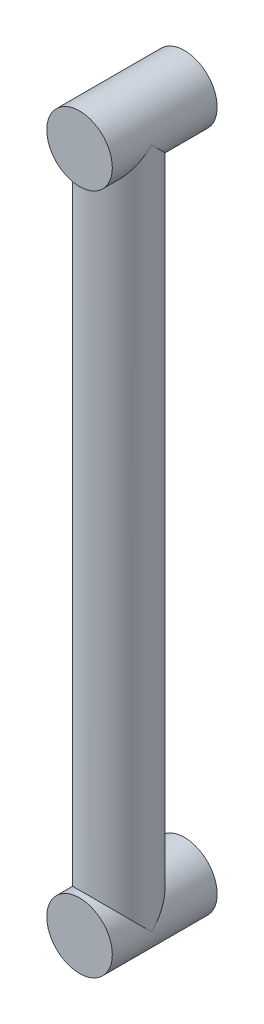
SolidWorks part; units mm, degrees
ref_plane "前视基准面" through (0, 0, 0) normal (0, 0, 1) x (1, 0, 0)
ref_plane "上视基准面" through (0, 0, 0) normal (0, 1, 0) x (1, 0, 0)
ref_plane "右视基准面" through (0, 0, 0) normal (1, 0, 0) x (0, 0, -1)
sketch "草图1" plane through (0, 0, 0) normal (0, 0, 1) x (1, 0, 0)
  circle A0 centre (0, 0) radius 250
extrude "凸台-拉伸1" add sketch "草图1" along normal blind 800
sketch "草图2" plane through (0, 0, 0) normal (0, 1, 0) x (1, 0, 0)
  circle A0 centre (0, -500) radius 250
  dimension "D1" = 500
extrude "凸台-拉伸2" add sketch "草图2" along normal blind 5200
ref_axis "基准轴1" through (0, 5200, 500) along (0, -1, 0)
pattern_linear "阵列(线性)1" count 2 spacing 5200 along (0, 1, 0) of "凸台-拉伸1"
ref_axis "基准轴2" through (0, 5200, 800) along (0, 0, -1)
ref_axis "基准轴3" through (0, 0, 800) along (0, 0, -1)
ref_point "点2"
ref_point "点3"
